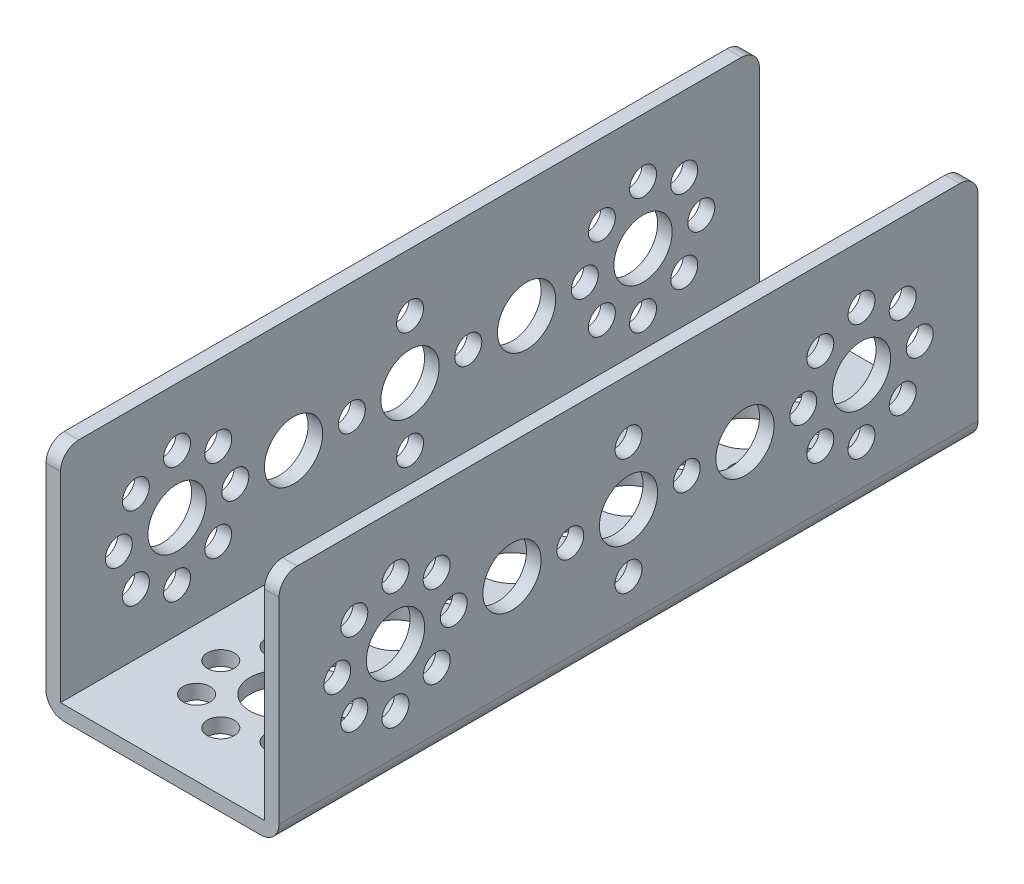
SolidWorks part; units mm, degrees
material "2024 Alloy"
ref_plane "Front Plane" through (0, 0, 0) normal (0, 0, 1) x (1, 0, 0)
ref_plane "Top Plane" through (0, 0, 0) normal (0, 1, 0) x (1, 0, 0)
ref_plane "Right Plane" through (0, 0, 0) normal (1, 0, 0) x (0, 0, -1)
ref_plane "Plane1" through (16, 0, 0) normal (1, 0, 0) x (0, 0, -1)
sketch "Sketch1" plane through (16, 0, 0) normal (1, 0, 0) x (0, 0, -1)
  line L0 (-16, 32) -> (-16, 0)
  line L1 (-16, 0) -> (80, 0)
  line L2 (80, 0) -> (80, 32)
  line L3 (80, 32) -> (-16, 32)
extrude "Boss-Extrude1" add sketch "Sketch1" against normal blind 32
sketch "Sketch2" plane through (0, 0, -80) normal (0, 0, -1) x (-1, 0, 0)
  line L0 (14, 32) -> (-14, 32)
  line L1 (-14, 32) -> (-14, 2)
  line L2 (-14, 2) -> (14, 2)
  line L3 (14, 2) -> (14, 32)
extrude "Cut-Extrude1" cut sketch "Sketch2" against normal through all
hole_wizard "Ø8.0 (8) Diameter Hole1" positions "Sketch4" profile "Sketch3" hole size "Ø8.0" standard "ANSI Metric"
sketch "Sketch4" plane through (-16, 0, 0) normal (-1, 0, 0) x (0, 0, 1)
  point P0 (-64, 16)
  point P1 (-32, 16)
  point P2 (-16, 16)
  point P3 (-48, 16)
  point P4 (0, 16)
sketch "Sketch3" plane through (-16, 16, -64) normal (0, 1, 0) x (0, 0, 1)
  line L0 (0, 0) -> (0, 2)
  line L1 (0, 2) -> (4, 2)
  line L2 (4, 2) -> (4, 0)
  line L5 (4, 0) -> (0, 0)
  line L11 (0, -6.35) -> (0, 107.95) construction
  dimension "Thru Hole Dia." = 8
  dimension "Thru Hole Depth" = 2
hole_wizard "Ø3.7 (3.7) Diameter Hole1" positions "Sketch6" profile "Sketch5" hole size "Ø3.7" standard "ANSI Metric"
sketch "Sketch6" plane through (-16, 0, 0) normal (-1, 0, 0) x (0, 0, 1)
  point P0 (0, 24)
  point P1 (0, 8)
  point P2 (-8, 16)
  point P3 (8, 16)
  point P4 (-5.6569, 21.6569)
  point P5 (5.6569, 21.6569)
  point P6 (5.6569, 10.3431)
  point P7 (-5.6569, 10.3431)
  point P8 (-64, 24)
  point P9 (-64, 8)
  point P10 (-72, 16)
  point P11 (-56, 16)
  point P12 (-69.6569, 21.6569)
  point P13 (-58.3431, 21.6569)
  point P14 (-58.3431, 10.3431)
  point P15 (-69.6569, 10.3431)
  point P16 (-32, 24)
  point P17 (-40, 16)
  point P18 (-32, 8)
  point P19 (-24, 16)
sketch "Sketch5" plane through (-16, 24, 0) normal (0, 1, 0) x (0, 0, 1)
  line L0 (0, 0) -> (0, 2)
  line L1 (0, 2) -> (1.85, 2)
  line L2 (1.85, 2) -> (1.85, 0)
  line L5 (1.85, 0) -> (0, 0)
  line L11 (0, -6.35) -> (0, 107.95) construction
  dimension "Thru Hole Dia." = 3.7
  dimension "Thru Hole Depth" = 2
hole_wizard "Ø3.7 (3.7) Diameter Hole2" positions "Sketch8" profile "Sketch7" hole size "Ø3.7" standard "ANSI Metric"
sketch "Sketch8" plane through (0, 0, 0) normal (0, -1, 0) x (-1, 0, 0)
  point P0 (8, 0)
  point P1 (5.6569, 5.6569)
  point P2 (0, 8)
  point P3 (-5.6569, 5.6569)
  point P4 (-8, 0)
  point P5 (-5.6569, -5.6569)
  point P6 (0, -8)
  point P7 (5.6569, -5.6569)
  point P8 (8, 64)
  point P9 (5.6569, 69.6569)
  point P10 (0, 72)
  point P11 (-5.6569, 69.6569)
  point P12 (-8, 64)
  point P13 (-5.6569, 58.3431)
  point P14 (0, 56)
  point P15 (5.6569, 58.3431)
  point P16 (8, 32)
  point P17 (0, 40)
  point P18 (-8, 32)
  point P19 (0, 24)
sketch "Sketch7" plane through (-8, 0, 0) normal (1, 0, 0) x (0, 0, -1)
  line L0 (0, 0) -> (0, 32)
  line L1 (0, 32) -> (1.85, 32)
  line L2 (1.85, 32) -> (1.85, 0)
  line L5 (1.85, 0) -> (0, 0)
  line L11 (0, -6.35) -> (0, 107.95) construction
  dimension "Thru Hole Dia." = 3.7
  dimension "Thru Hole Depth" = 32
hole_wizard "Ø8.0 (8) Diameter Hole2" positions "Sketch10" profile "Sketch9" hole size "Ø8.0" standard "ANSI Metric"
sketch "Sketch10" plane through (0, 0, 0) normal (0, -1, 0) x (-1, 0, 0)
  point P0 (0, 0)
  point P1 (0, 64)
  point P2 (0, 32)
  point P3 (0, 16)
  point P4 (0, 48)
sketch "Sketch9" plane through (0, 0, 0) normal (1, 0, 0) x (0, 0, -1)
  line L0 (0, 0) -> (0, 32)
  line L1 (0, 32) -> (4, 32)
  line L2 (4, 32) -> (4, 0)
  line L5 (4, 0) -> (0, 0)
  line L11 (0, -6.35) -> (0, 107.95) construction
  dimension "Thru Hole Dia." = 8
  dimension "Thru Hole Depth" = 32
hole_wizard "Ø8.0 (8) Diameter Hole3" positions "Sketch12" profile "Sketch11" hole size "Ø8.0" standard "ANSI Metric"
sketch "Sketch12" plane through (14, 0, 0) normal (-1, 0, 0) x (0, 0, 1)
  point P0 (-32, 16)
sketch "Sketch11" plane through (14, 16, -32) normal (0, 1, 0) x (0, 0, 1)
  line L0 (0, 0) -> (0, 2)
  line L1 (0, 2) -> (4, 2)
  line L2 (4, 2) -> (4, 0)
  line L5 (4, 0) -> (0, 0)
  line L11 (0, -6.35) -> (0, 107.95) construction
  dimension "Thru Hole Dia." = 8
  dimension "Thru Hole Depth" = 2
hole_wizard "Ø8.0 (8) Diameter Hole4" positions "Sketch14" profile "Sketch13" hole size "Ø8.0" standard "ANSI Metric"
sketch "Sketch14" plane through (16, 0, 0) normal (1, 0, 0) x (0, 0, -1)
  point P0 (64, 16)
  point P1 (16, 16)
  point P2 (48, 16)
  point P3 (0, 16)
sketch "Sketch13" plane through (16, 16, -64) normal (0, 1, 0) x (0, 0, -1)
  line L0 (0, 0) -> (0, 32)
  line L1 (0, 32) -> (4, 32)
  line L2 (4, 32) -> (4, 0)
  line L5 (4, 0) -> (0, 0)
  line L11 (0, -6.35) -> (0, 107.95) construction
  dimension "Thru Hole Dia." = 8
  dimension "Thru Hole Depth" = 32
hole_wizard "Ø3.7 (3.7) Diameter Hole3" positions "Sketch16" profile "Sketch15" hole size "Ø3.7" standard "ANSI Metric"
sketch "Sketch16" plane through (16, 0, 0) normal (1, 0, 0) x (0, 0, -1)
  point P0 (0, 24)
  point P1 (0, 8)
  point P2 (8, 16)
  point P3 (-8, 16)
  point P4 (5.6569, 21.6569)
  point P5 (-5.6569, 21.6569)
  point P6 (-5.6569, 10.3431)
  point P7 (5.6569, 10.3431)
  point P8 (64, 24)
  point P9 (64, 8)
  point P10 (72, 16)
  point P11 (56, 16)
  point P12 (69.6569, 21.6569)
  point P13 (58.3431, 21.6569)
  point P14 (58.3431, 10.3431)
  point P15 (69.6569, 10.3431)
  point P16 (32, 24)
  point P17 (40, 16)
  point P18 (32, 8)
  point P19 (24, 16)
sketch "Sketch15" plane through (16, 24, 0) normal (0, 1, 0) x (0, 0, -1)
  line L0 (0, 0) -> (0, 32)
  line L1 (0, 32) -> (1.85, 32)
  line L2 (1.85, 32) -> (1.85, 0)
  line L5 (1.85, 0) -> (0, 0)
  line L11 (0, -6.35) -> (0, 107.95) construction
  dimension "Thru Hole Dia." = 3.7
  dimension "Thru Hole Depth" = 32
fillet "Fillet1" radius 2.5 6 edges at (-16, 0, -32) (-15, 32, -80) (-15, 32, 16) (16, 0, -32) (15, 32, 16) (15, 32, -80) tangent propagation no
